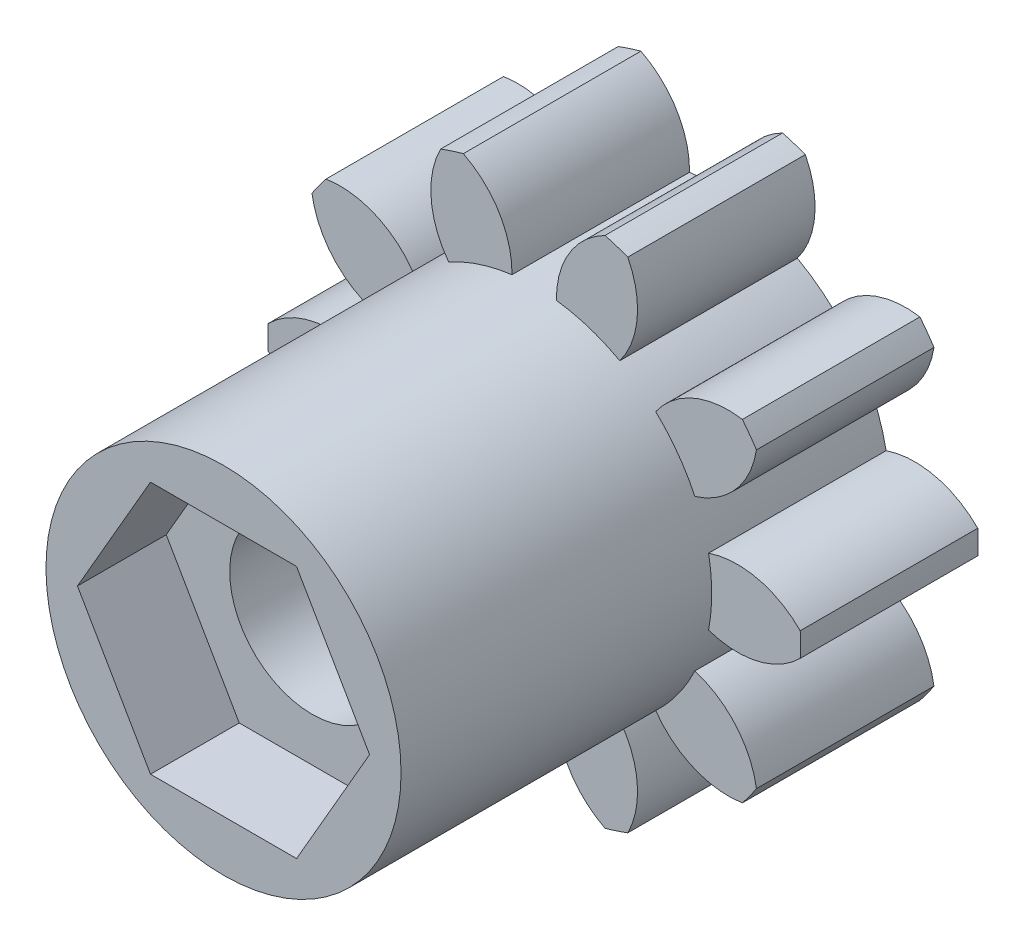
SolidWorks part; units mm, degrees
ref_plane "Front" through (0, 0, 0) normal (0, 0, 1) x (1, 0, 0)
ref_plane "Top" through (0, 0, 0) normal (0, 1, 0) x (1, 0, 0)
ref_plane "Right" through (0, 0, 0) normal (1, 0, 0) x (0, 0, -1)
sketch "Sketch1" plane through (0, 0, 0) normal (0, 0, 1) x (1, 0, 0)
  circle A0 centre (0, 0) radius 2
  circle A1 centre (0, 0) radius 6
extrude "Boss-Extrude1" add sketch "Sketch1" along normal blind 4
sketch "Sketch4" plane through (0, 0, 0) normal (0, 0, 1) x (1, 0, 0)
  line L0 (0, 4) -> (2.5, 4) construction
  line L1 (0, 4) -> (-2.5, 4) construction
  circle A0 centre (0, 0) radius 4
  circle A1 centre (0, 0) radius 6.5
  circle A2 centre (2.5, 4) radius 2
  circle A3 centre (-2.5, 4) radius 2
extrude "Cut-Extrude2" cut sketch "Sketch4" along normal through all contours A3 A0 A2 A1 region at (0, 5.5467, 0)
pattern_circular "CirPattern2" count 10 over 360 about axis through (0, 0, 4) along (0, 0, -1) of "Cut-Extrude2"
sketch "Sketch10" plane through (0, 0, 0) normal (0, 0, 1) x (1, 0, 0)
  line L0 (0, 4) -> (-5.1235, 4) construction
  line L1 (0, 4) -> (5.1235, 4) construction
  circle A0 centre (0, 0) radius 6.5
  circle A1 centre (0, 0) radius 4
  circle A2 centre (-2.5617, 4) radius 2.25
  circle A3 centre (2.5617, 4) radius 2.25
sketch "Sketch11" plane through (0, 0, 0) normal (0, 0, 1) x (1, 0, 0)
  circle A0 centre (0, 0) radius 4
extrude "Boss-Extrude2" add sketch "Sketch11" along normal blind 11
sketch "Sketch12" plane through (0, 0, 0) normal (0, 0, 1) x (1, 0, 0)
  line L1 (3.2909, 0) -> (1.6454, 2.85)
  line L2 (1.6454, 2.85) -> (-1.6454, 2.85)
  line L3 (-1.6454, 2.85) -> (-3.2909, 0)
  line L4 (-3.2909, 0) -> (-1.6454, -2.85)
  line L5 (-1.6454, -2.85) -> (1.6454, -2.85)
  line L6 (1.6454, -2.85) -> (3.2909, 0)
  circle A0 centre (0, 0) radius 2.85 construction
  dimension "D1" = 5.7
extrude "Cut-Extrude3" cut sketch "Sketch12" against normal blind 2 from offset 11
sketch "Sketch13" plane through (0, 0, 0) normal (0, 0, 1) x (1, 0, 0)
  line L0 (0, 0) -> (0, 0.95) construction
  line L2 (1.6, 0.95) -> (-1.6, 0.95)
  arc A0 (1.6, 0.95) -> (-1.6, 0.95) centre (0, 0) cw
extrude "Cut-Extrude4" cut sketch "Sketch13" along normal through all contours A0 L2 region at (0, -0.3098, 0)
